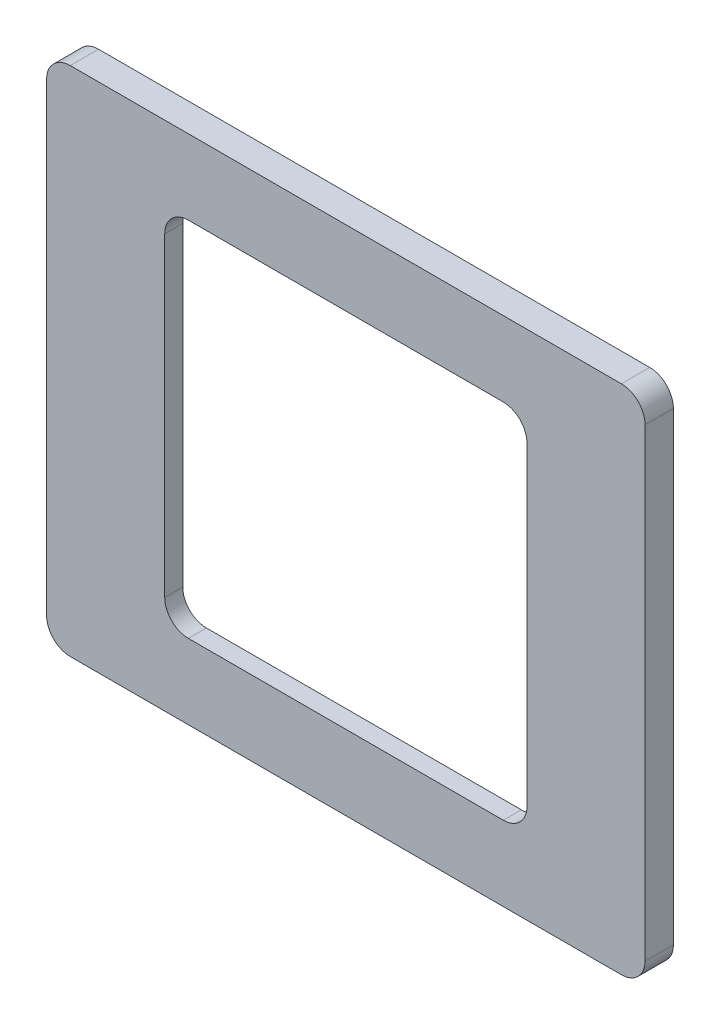
SolidWorks part; units mm, degrees
ref_plane "Front Plane" through (0, 0, 0) normal (0, 0, 1) x (1, 0, 0)
ref_plane "Top Plane" through (0, 0, 0) normal (0, 1, 0) x (1, 0, 0)
ref_plane "Right Plane" through (0, 0, 0) normal (1, 0, 0) x (0, 0, -1)
sketch "Sketch1" plane through (0, 0, 0) normal (0, 1, 0) x (1, 0, 0)
  line L1 (38, 3.6) -> (-38, 3.6)
  line L2 (38, 3.6) -> (38, 0)
  line L3 (-38, 3.6) -> (-38, 0)
  line L5 (0, -1.941) -> (0, 24.0569) construction
  line L9 (-38, 0) -> (38, 0)
  point P19 (0, 0)
  dimension "D2" = 76
  dimension "D5" = 3.6
extrude "Boss-Extrude1" add sketch "Sketch1" along normal blind 65
ref_plane "Plane1" through (0, 0, -3.6) normal (0, 0, -1) x (-1, 0, 0)
sketch "Sketch2" plane through (0, 0, -3.6) normal (0, 0, -1) x (-1, 0, 0)
  line L0 (0, 1.98) -> (0, -1.98) construction
  line L1 (25.8, 6.7) -> (-25.8, 6.7)
  line L2 (25.8, 6.7) -> (25.8, 58.3)
  line L3 (25.8, 58.3) -> (-25.8, 58.3)
  line L4 (-25.8, 6.7) -> (-25.8, 58.3)
  line L5 (25.8, 6.7) -> (-25.8, 58.3) construction
  line L6 (25.8, 58.3) -> (-25.8, 6.7) construction
  line L7 (0, 0) -> (0, 65) construction
  line L8 (-38, 65) -> (38, 65) construction
  point P0 (0, 32.5)
  point P13 (0, 32.5)
  dimension "D1" = 51.6
extrude "Cut-Extrude1" cut sketch "Sketch2" against normal blind 1.31
sketch "Sketch4" plane through (0, 0, -3.6) normal (0, 0, -1) x (-1, 0, 0)
  circle A0 centre (25.8, 6.7) radius 1
  circle A1 centre (25.8, 58.3) radius 1
  circle A2 centre (-25.8, 6.7) radius 1
  circle A3 centre (-25.8, 58.3) radius 1
  dimension "D1" = 2
extrude "Cut-Extrude3" cut sketch "Sketch4" against normal up to surface (1.31 mm away) up to face at (0, 32.5, -2.29)
sketch "Sketch3" plane through (0, 0, -2.29) normal (0, 0, -1) x (-1, 0, 0)
  line L1 (23, 9.5) -> (-23, 9.5)
  line L2 (23, 9.5) -> (23, 55.5)
  line L3 (23, 55.5) -> (-23, 55.5)
  line L4 (-23, 9.5) -> (-23, 55.5)
  line L5 (23, 9.5) -> (-23, 55.5) construction
  line L6 (23, 55.5) -> (-23, 9.5) construction
  point P0 (0, 32.5)
  dimension "D1" = 46
extrude "Cut-Extrude2" cut sketch "Sketch3" against normal through all
fillet "Fillet1" radius 3 8 edges at (-23, 55.5, -1.145) (23, 55.5, -1.145) (23, 9.5, -1.145) (-23, 9.5, -1.145) (38, 0, -1.8) (-38, 0, -1.8) (-38, 65, -1.8) (38, 65, -1.8)
fillet "Fillet2" radius 2 8 edges at (24.8, 6.7, -2.945) (25.8, 7.7, -2.945) (25.8, 57.3, -2.945) (24.8, 58.3, -2.945) (-24.8, 58.3, -2.945) (-25.8, 57.3, -2.945) (-25.8, 7.7, -2.945) (-24.8, 6.7, -2.945)
